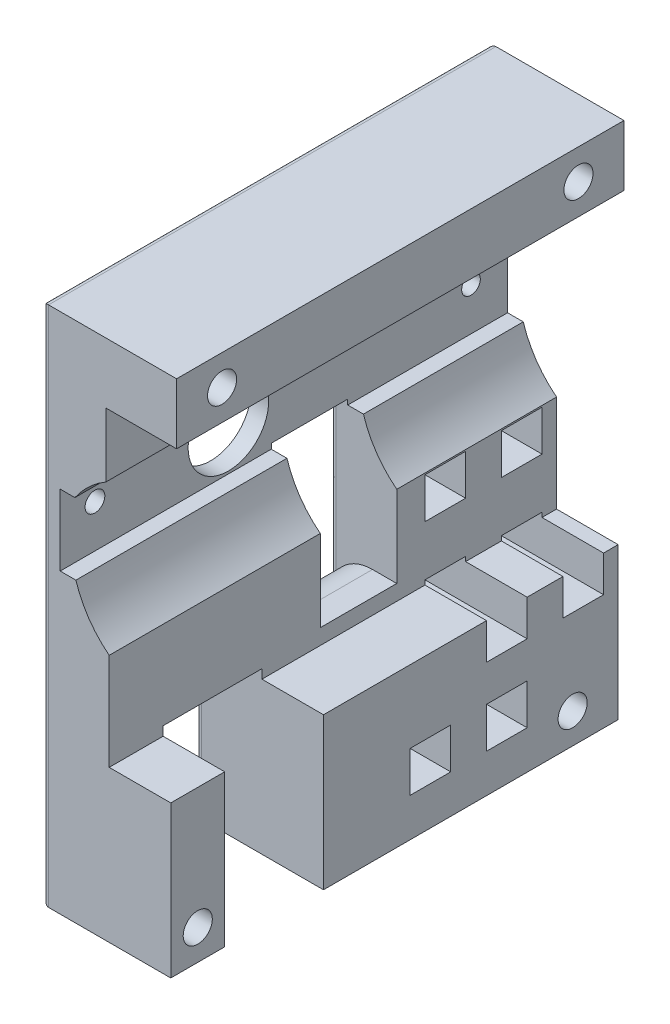
SolidWorks part; units mm, degrees
ref_plane "Front" through (0, 0, 0) normal (0, 0, 1) x (1, 0, 0)
ref_plane "Top" through (0, 0, 0) normal (0, 1, 0) x (1, 0, 0)
ref_plane "Right" through (0, 0, 0) normal (1, 0, 0) x (0, 0, -1)
sketch "Profile" plane through (0, 0, 0) normal (0, 0, 1) x (1, 0, 0)
  line L0 (9.3013, -54.1947) -> (9.3013, -29.1947)
  line L1 (-11.8487, -54.1947) -> (9.3013, -54.1947)
  line L2 (-11.8487, -54.1947) -> (-11.8487, 31.8453)
  line L3 (-11.8487, 31.8453) -> (10.2613, 31.8453)
  line L4 (10.2613, 21.8453) -> (10.2613, 31.8453)
  line L7 (9.3013, -29.1947) -> (-0.8487, -29.1947)
  line L8 (-0.8487, -29.1947) -> (-0.8487, -13.1947)
  line L10 (10.2613, 21.8453) -> (-1.3887, 21.8453)
  line L11 (-1.3887, 21.8453) -> (-1.3887, 11.2835)
  line L12 (-6.5097, 6.4953) -> (-8.9287, 6.4953)
  line L13 (-8.9287, 6.4953) -> (-8.9287, -5.2047)
  line L14 (-8.9287, -5.2047) -> (-6.3407, -5.2047)
  arc A0 (-6.3407, -5.2047) -> (-0.8487, -13.1947) centre (9.1965, -0.4075) ccw
  arc A1 (-6.5097, 6.4953) -> (-1.3887, 11.2835) centre (6.8957, -2.7089) cw
  point P0 (0, 0)
  dimension "D15" = 16.261
  dimension "D16" = 16.261
  dimension "D1" = 86.04
  dimension "D2" = 22.11
  dimension "D3" = 10
  dimension "D4" = 25
  dimension "D5" = 21.15
  dimension "D6" = 10.15
  dimension "D7" = 11.65
  dimension "D8" = 10.5617
  dimension "D9" = 16
  dimension "D10" = 2.588
  dimension "D11" = 11.7
  dimension "D12" = 2.4191
  dimension "D13" = 5.492
  dimension "D14" = 23.99
extrude "ProfileExtrude" add sketch "Profile" along normal blind 73.76
sketch "HoseWindow" plane through (-11.8487, 0, 0) normal (-1, 0, 0) x (0, 0, 1)
  line L0 (73.76, -54.1947) -> (0, -54.1947) construction
  line L1 (64.87, -54.1947) -> (48.58, -54.1947)
  line L2 (64.87, -54.1947) -> (64.87, -27.6947)
  line L3 (64.87, -27.6947) -> (48.58, -27.6947)
  line L4 (48.58, -54.1947) -> (48.58, -27.6947)
  dimension "D1" = 16.29
  dimension "D2" = 26.5
  dimension "D3" = 8.89
extrude "HoseWindowCut" cut sketch "HoseWindow" against normal through all
sketch "CageScrews" plane through (-11.8487, 0, 0) normal (-1, 0, 0) x (0, 0, 1)
  line L0 (73.76, 31.8453) -> (0, 31.8453) construction
  line L1 (0, 31.8453) -> (0, -54.1947) construction
  line L2 (73.76, 31.8453) -> (73.76, -54.1947) construction
  line L3 (73.76, -54.1947) -> (64.87, -54.1947) construction
  line L4 (48.58, -54.1947) -> (0, -54.1947) construction
  circle A0 centre (7.5, 26.8453) radius 2.4
  circle A1 centre (66.26, 26.8453) radius 2.4
  circle A2 centre (7.5, -49.1947) radius 2.4
  circle A3 centre (69.31, -49.1947) radius 2.4
  dimension "D1" = 4.8
  dimension "D2" = 5
  dimension "D3" = 7.5
  dimension "D4" = 7.5
  dimension "D5" = 5
  dimension "D6" = 5
  dimension "D7" = 4.45
  dimension "D8" = 5
  dimension "D9" = 7.5
extrude "CageScrewsCut" cut sketch "CageScrews" against normal through all
sketch "AxleHole" plane through (-11.8487, 0, 0) normal (-1, 0, 0) x (0, 0, 1)
  line L0 (46.03, -4.7837) -> (46.03, 6.7405) construction
  line L1 (47.361, 8.3595) -> (47.361, 6.7405)
  line L2 (47.361, 6.7405) -> (44.699, 6.7405)
  line L3 (44.699, 6.7405) -> (44.699, 8.3595)
  line L5 (48.58, -54.1947) -> (0, -54.1947) construction
  line L6 (0, 31.8453) -> (0, -54.1947) construction
  line L7 (39.391, 1.8553) -> (52.669, 1.8553) construction
  arc A0 (44.699, 8.3595) -> (47.361, 8.3595) centre (46.03, 1.8553) ccw
  dimension "D1" = 13.278
  dimension "D2" = 1.331
  dimension "D3" = 1.619
  dimension "D4" = 1.619
  dimension "D5" = 46.03
  dimension "D6" = 56.05
extrude "AxleHoleCut" cut sketch "AxleHole" against normal through all
sketch "SetScrewHoles" plane through (-11.8487, 0, 0) normal (-1, 0, 0) x (0, 0, 1)
  line L0 (47.361, 6.7405) -> (44.699, 6.7405) construction
  circle A0 centre (6.03, 1.8553) radius 1.5394
  circle A1 centre (68.03, 1.8553) radius 1.629
  point P6 (46.03, 6.7405)
  point P7 (46.03, 6.7405)
  dimension "D1" = 22
  dimension "D2" = 40
extrude "SetScrewHolesCut" cut sketch "SetScrewHoles" against normal through all
sketch "VelocityWindow" plane through (-11.8487, 0, 0) normal (-1, 0, 0) x (0, 0, 1)
  line L0 (73.76, 31.8453) -> (73.76, -54.1947) construction
  line L1 (38.96, -26.6447) -> (26.35, -26.6447)
  line L2 (38.96, -26.6447) -> (38.96, -4.3547)
  line L3 (38.96, -4.3547) -> (26.35, -4.3547)
  line L4 (26.35, -26.6447) -> (26.35, -4.3547)
  line L5 (38.96, -26.6447) -> (26.35, -4.3547) construction
  line L6 (38.96, -4.3547) -> (26.35, -26.6447) construction
  line L7 (48.58, -54.1947) -> (0, -54.1947) construction
  point P0 (32.655, -15.4997)
  dimension "D1" = 12.61
  dimension "D2" = 22.29
  dimension "D3" = 34.8
  dimension "D4" = 27.55
extrude "VelocityWindowCut" cut sketch "VelocityWindow" against normal through all
fillet "Fillet3" radius 7 1 edges at (-11.8487, -26.6447, 32.655)
sketch "TriggerRackSlotCut" plane through (-11.8487, 0, 0) normal (-1, 0, 0) x (0, 0, 1)
  line L0 (15, -41.1447) -> (21.7, -41.1447)
  line L1 (15, -41.1447) -> (15, -47.8447)
  line L2 (21.7, -41.1447) -> (21.7, -47.8447)
  line L3 (15, -47.8447) -> (21.7, -47.8447)
  line L4 (0, 31.8453) -> (0, -54.1947) construction
  line L5 (27.6, -41.1447) -> (34.3, -41.1447)
  line L6 (27.6, -41.1447) -> (27.6, -47.8447)
  line L7 (34.3, -41.1447) -> (34.3, -47.8447)
  line L8 (27.6, -47.8447) -> (34.3, -47.8447)
  line L9 (2.4, -28.4447) -> (9.1, -28.4447)
  line L10 (2.4, -28.4447) -> (2.4, -35.1447)
  line L11 (9.1, -28.4447) -> (9.1, -35.1447)
  line L12 (2.4, -35.1447) -> (9.1, -35.1447)
  line L13 (15, -28.4447) -> (21.7, -28.4447)
  line L14 (15, -28.4447) -> (15, -35.1447)
  line L15 (21.7, -28.4447) -> (21.7, -35.1447)
  line L16 (48.58, -54.1947) -> (0, -54.1947) construction
  line L17 (15, -35.1447) -> (21.7, -35.1447)
  line L18 (15, -41.1447) -> (27.6, -41.1447) construction
  line L19 (15, -41.1447) -> (15, -28.4447) construction
  line L20 (2.4, -13.4447) -> (9.1, -13.4447)
  line L21 (2.4, -13.4447) -> (2.4, -20.1447)
  line L22 (9.1, -13.4447) -> (9.1, -20.1447)
  line L23 (2.4, -20.1447) -> (9.1, -20.1447)
  line L24 (15, -13.4447) -> (21.7, -13.4447)
  line L25 (15, -13.4447) -> (15, -20.1447)
  line L26 (21.7, -13.4447) -> (21.7, -20.1447)
  line L27 (15, -20.1447) -> (21.7, -20.1447)
  line L28 (15, -28.4447) -> (2.4, -28.4447) construction
  line L43 (27.6, -28.4447) -> (34.3, -28.4447) [skipped]
  line L44 (27.6, -28.4447) -> (27.6, -35.1447) [skipped]
  line L45 (34.3, -28.4447) -> (34.3, -35.1447) [skipped]
  line L46 (27.6, -35.1447) -> (34.3, -35.1447) [skipped]
  dimension "D1" = 6.35
  dimension "D2" = 15
  dimension "D3" = 6.7
  dimension "D4" = 6.7
  dimension "D7" = 2
  dimension "D5" = 12.6
  dimension "D6" = 12.7
  dimension "D9" = 12.6
  dimension "D8" = 2
extrude "RackSlotCut" cut sketch "TriggerRackSlotCut" against normal through all
fillet "Fillet4" radius 1 35 edges at (-11.8487, -31.7947, 21.7) (-11.8487, -28.4447, 18.35) (-11.8487, -31.7947, 15) (-11.8487, -35.1447, 18.35) (-11.8487, -47.8447, 18.35) (-11.8487, -44.4947, 15) (-11.8487, -41.1447, 18.35) (-11.8487, -44.4947, 21.7) (-11.8487, -47.8447, 30.95) (-11.8487, -44.4947, 34.3) (-11.8487, -18.9997, 38.96) (-11.8487, -4.3547, 32.655) (-11.8487, -18.9997, 26.35) (-11.8487, -11.1747, 0) (-11.8487, -54.1947, 24.29) (-11.8487, -40.9447, 48.58) (-11.8487, -27.6947, 56.725) (-11.8487, -40.9447, 64.87) (-11.8487, -54.1947, 69.315) (-11.8487, -11.1747, 73.76) (-11.8487, 31.8453, 36.88) (-11.8487, -44.4947, 27.6) (-11.8487, -41.1447, 30.95) (-11.8487, -35.1447, 5.75) (-11.8487, -31.7947, 2.4) (-11.8487, -31.7947, 9.1) (-11.8487, -28.4447, 5.75) (-11.8487, -13.4447, 18.35) (-11.8487, -16.7947, 21.7) (-11.8487, -20.1447, 18.35) (-11.8487, -16.7947, 15) (-11.8487, -16.7947, 2.4) (-11.8487, -20.1447, 5.75) (-11.8487, -16.7947, 9.1) (-11.8487, -13.4447, 5.75)
equation "\"CageLeftBottomEdge\"=21.15mm"
equation "\"CageLeftTopEdge\"=22.11mm"
equation "\"CageHeight\"=86.04mm"
equation "\"CageLength\"=73.76mm"
equation "\"CageTopScrewClearance\"=10mm"
equation "\"CageLeftTopDepth\"= 11.65mm"
equation "\"CageLeftBottomDepth\"=10.15mm"
equation "\"CageLeftTopHeight\"=10.56175mm"
equation "\"CageLeftBottomHeight\"=16mm"
equation "\"CageLeftTopChannelDepth\"=2.41908mm"
equation "\"CageLeftBottomChannelDepth\"=2.588mm"
equation "\"CageLeftChannelHeight\"=11.7mm"
equation "\"CageChanRelHeight\"=23.99mm"
equation "\"CageChanRelDepth\"=5.492mm"
equation "\"CageChamberRadius\"=16.261mm"
equation "\"CageScrewDiameter\"=4.8mm"
equation "\"CageSetScrewDiameter\"=3.5mm"
equation "\"CageAxleRadius\"=6.639mm"
equation "\"CageAxleKeyHeight\"=1.619mm"
equation "\"CageAxleKeyWidth\"=2.662mm"
equation "\"CageHoseWindowWidth\"=16.29mm"
equation "\"CageHoseWindowHeight\"=26.5mm"
equation "\"CageHoseWindow-Edge\"=8.89mm"
equation "\"CageScrew-VerticalEdge\"=5.0mm"
equation "\"CageScrew-HorizontalEdge\"=7.5mm"
equation "\"CageScrew-HoseCornerScrewEdge\"=4.45mm"
equation "\"CageAxle-BottomEdge\"=56.05mm"
equation "\"CageBackSetScrew-Axle\"=40mm"
equation "\"CageFrontSetScrew-Axle\"=22mm"
equation "\"CageVelocityWindow-BackEdge\"=34.8mm"
equation "\"CageVelocityWindow-BottomEdge\"=27.55mm"
equation "\"CageVelocityWindowHeight\"=22.29mm"
equation "\"CageVelocityWindowWidth\"=12.61mm"
equation "\"D11@Profile\" = \"CageLeftChannelHeight\""
equation "\"D10@Profile\" = \"CageLeftBottomChannelDepth\""
equation "\"D12@Profile\" = \"CageLeftTopChannelDepth\""
equation "\"D8@Profile\" = \"CageLeftTopHeight\""
equation "\"D9@Profile\" = \"CageLeftBottomHeight\""
equation "\"D6@Profile\" = \"CageLeftBottomDepth\""
equation "\"D7@Profile\" = \"CageLeftTopDepth\""
equation "\"D3@Profile\" = \"CageTopScrewClearance\""
equation "\"CageBottomScrewClearance\"=25mm"
equation "\"D4@Profile\" = \"CageBottomScrewClearance\""
equation "\"D5@Profile\" = \"CageLeftBottomEdge\""
equation "\"D2@Profile\" = \"CageLeftTopEdge\""
equation "\"D1@Profile\" = \"CageHeight\""
equation "\"D13@Profile\" = \"CageChanRelDepth\""
equation "\"D14@Profile\" = \"CageChanRelHeight\""
equation "\"D15@Profile\" = \"CageChamberRadius\""
equation "\"D16@Profile\" = \"CageChamberRadius\""
equation "\"D1@ProfileExtrude\"= \"CageLength\""
equation "\"D3@HoseWindow\" = \"CageHoseWindow-Edge\""
equation "\"D2@HoseWindow\" = \"CageHoseWindowHeight\""
equation "\"D1@HoseWindow\" = \"CageHoseWindowWidth\""
equation "\"D1@CageScrews\"= \"CageScrewDiameter\""
equation "\"D9@CageScrews\" = \"CageScrew-HorizontalEdge\""
equation "\"D7@CageScrews\" = \"CageScrew-HoseCornerScrewEdge\""
equation "\"D4@CageScrews\" = \"CageScrew-HorizontalEdge\""
equation "\"D6@CageScrews\"= \"CageScrew-VerticalEdge\""
equation "\"D5@CageScrews\"= \"CageScrew-VerticalEdge\""
equation "\"D8@CageScrews\"= \"CageScrew-VerticalEdge\""
equation "\"D2@CageScrews\"= \"CageScrew-VerticalEdge\""
equation "\"D1@AxleHole\" = \"CageAxleRadius\" * 2"
equation "\"D4@AxleHole\" = \"CageAxleKeyHeight\""
equation "\"D3@AxleHole\" = \"CageAxleKeyHeight\""
equation "\"D2@AxleHole\" = \"CageAxleKeyWidth\" / 2"
equation "\"CageAxle-FrontEdge\"=46.03mm"
equation "\"D6@AxleHole\" = \"CageAxle-BottomEdge\""
equation "\"D5@AxleHole\" = \"CageAxle-FrontEdge\""
equation "\"D2@SetScrewHoles\" = \"CageBackSetScrew-Axle\""
equation "\"D1@SetScrewHoles\" = \"CageFrontSetScrew-Axle\""
equation "\"D1@VelocityWindow\" = \"CageVelocityWindowWidth\""
equation "\"D2@VelocityWindow\" = \"CageVelocityWindowHeight\""
equation "\"D3@VelocityWindow\" = \"CageVelocityWindow-BackEdge\""
equation "\"D4@VelocityWindow\"= \"CageVelocityWindow-BottomEdge\""
equation "\"TriggerSlot-BottomEdge\"=6.35mm"
equation "\"D1@TriggerRackSlotCut\" = \"TriggerSlot-BottomEdge\""
equation "\"TriggerSlot-FrontEdge\"=15mm"
equation "\"TriggerSlotSize\"=6.7mm"
equation "\"D3@TriggerRackSlotCut\" = \"TriggerSlotSize\""
equation "\"D4@TriggerRackSlotCut\" = \"TriggerSlotSize\""
equation "\"D2@TriggerRackSlotCut\" = \"TriggerSlot-FrontEdge\""
